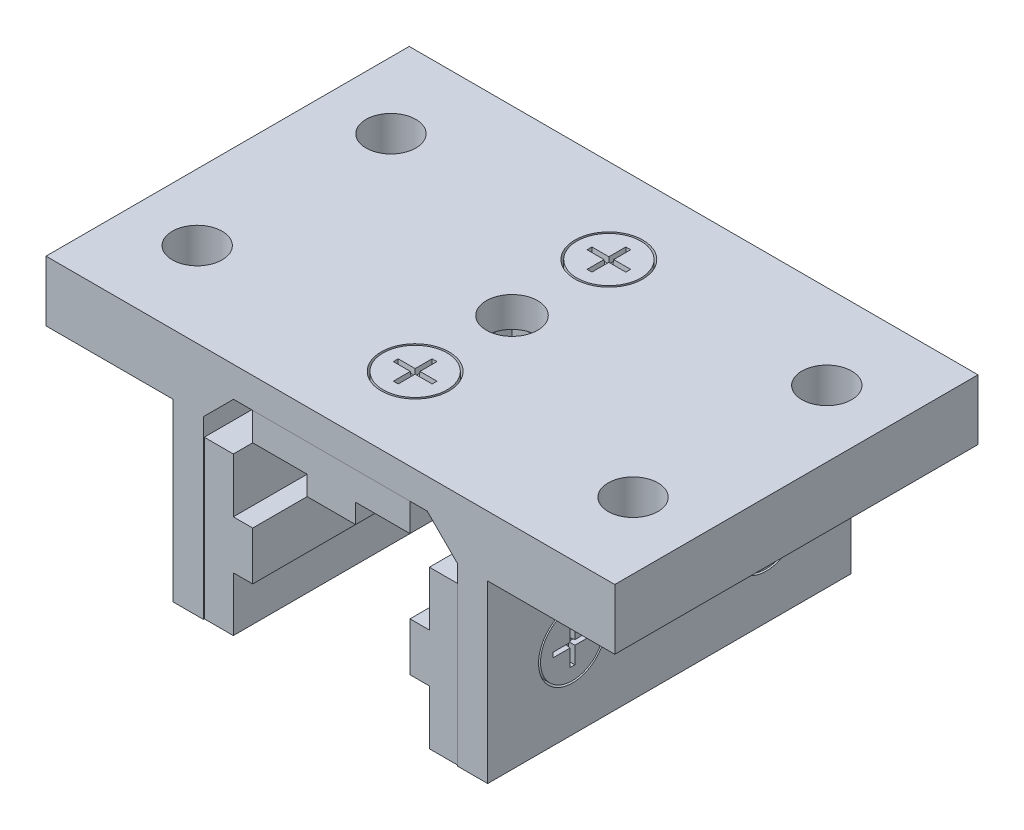
SolidWorks part; units mm, degrees
ref_plane "Front" through (0, 0, 0) normal (0, 0, 1) x (1, 0, 0)
ref_plane "Top" through (0, 0, 0) normal (0, 1, 0) x (1, 0, 0)
ref_plane "Right" through (0, 0, 0) normal (1, 0, 0) x (0, 0, -1)
sketch "Sketch1" plane through (0, 0, 0) normal (0, 0, 1) x (1, 0, 0)
  line L0 (-16.6624, 0) -> (-16.6624, 23.0124)
  line L1 (-20.6248, 30.9372) -> (20.6248, 30.9372)
  line L2 (-20.6248, 30.9372) -> (-20.6248, 0)
  line L3 (-20.6248, 0) -> (-16.6624, 0)
  line L4 (20.6248, 30.9372) -> (20.6248, 0)
  line L5 (-16.6624, 23.0124) -> (-12.7, 26.9748)
  line L6 (-12.7, 26.9748) -> (12.7, 26.9748)
  line L7 (12.7, 26.9748) -> (16.6624, 23.0124)
  line L8 (16.6624, 23.0124) -> (16.6624, 0)
  line L9 (16.6624, 0) -> (20.6248, 0)
  line L11 (-16.6624, 0) -> (16.6624, 0) construction
  dimension "D2" = 45
extrude "Boss-Extrude1" add sketch "Sketch1" along normal mid plane 47.625
sketch "Sketch2" plane through (0, 0, 0) normal (0, 0, 1) x (1, 0, 0)
  line L0 (-12.8524, 13.4874) -> (-12.8524, 20.6248)
  line L1 (-16.6624, 0) -> (-12.8524, 0)
  line L2 (-16.6624, 0) -> (-16.6624, 20.6248)
  line L3 (-16.6624, 20.6248) -> (-12.8524, 20.6248)
  line L4 (-12.8524, 0) -> (-12.8524, 7.1374)
  line L5 (-12.8524, 13.4874) -> (-10.3124, 13.4874)
  line L7 (-12.8524, 7.1374) -> (-10.3124, 7.1374)
  line L8 (-10.3124, 13.4874) -> (-10.3124, 7.1374)
  line L12 (-12.7, 26.9748) -> (12.7, 26.9748) construction
  line L13 (-10.3124, 26.9748) -> (10.3124, 26.9748)
  line L14 (-10.3124, 26.9748) -> (-10.3124, 23.1648)
  line L15 (-10.3124, 23.1648) -> (-3.175, 23.1648)
  line L16 (10.3124, 26.9748) -> (10.3124, 23.1648)
  line L17 (3.175, 23.1648) -> (10.3124, 23.1648)
  line L19 (-3.175, 23.1648) -> (-3.175, 20.6248)
  line L20 (-3.175, 20.6248) -> (3.175, 20.6248)
  line L21 (3.175, 23.1648) -> (3.175, 20.6248)
  point P14 (-10.3124, 10.3124)
  point P28 (0, 26.9748)
  dimension "Pad Wd" = 20.6248
  dimension "Pad Thick 1" = 6.35
  dimension "Pad Thick 2" = 3.81
  dimension "Pad Nose" = 6.35
extrude "Boss-Extrude2" add sketch "Sketch2" along normal mid plane 47.371 separate body
sketch "Sketch11" plane through (-10.3124, 0, 0) normal (1, 0, 0) x (0, 0, -1)
  line L0 (-23.6855, 13.4874) -> (23.6855, 13.4874) construction
  line L1 (-3.175, 13.4874) -> (3.175, 13.4874)
  line L2 (-3.175, 13.4874) -> (-3.175, 7.1374)
  line L3 (-3.175, 7.1374) -> (3.175, 7.1374)
  line L4 (3.175, 13.4874) -> (3.175, 7.1374)
  line L5 (-23.6855, 7.1374) -> (23.6855, 7.1374) construction
  point P8 (0, 13.4874)
extrude "Cut-Extrude5" cut sketch "Sketch11" against normal through all
sketch "Sketch12" plane through (0, 20.6248, 0) normal (0, -1, 0) x (1, 0, 0)
  line L0 (-3.175, 23.6855) -> (-3.175, -23.6855) construction
  line L1 (-3.175, 3.175) -> (3.175, 3.175)
  line L2 (-3.175, 3.175) -> (-3.175, -3.175)
  line L3 (-3.175, -3.175) -> (3.175, -3.175)
  line L4 (3.175, 3.175) -> (3.175, -3.175)
  line L5 (3.175, 23.6855) -> (3.175, -23.6855) construction
  point P8 (-3.175, 0)
extrude "Cut-Extrude6" cut sketch "Sketch12" against normal through all
mirror "Mirror1" about plane through (0, 0, 0) normal (1, 0, 0) of bodies 126 109
sketch "Sketch3" plane through (0, 30.9372, 0) normal (0, 1, 0) x (1, 0, 0)
  line L0 (0, -12.7) -> (0, 12.7) construction
  circle A0 centre (0, -12.7) radius 4.445
  circle A1 centre (0, -12.7) radius 4.191
extrude "Cut-Extrude1" cut sketch "Sketch3" against normal blind 1.9812
sketch "Sketch5" plane through (0, 30.9372, 0) normal (0, 1, 0) x (1, 0, 0)
  line L0 (0.3175, -12.3825) -> (2.54, -12.3825)
  line L1 (-0.3175, -10.16) -> (0.3175, -10.16)
  line L2 (-0.3175, -10.16) -> (-0.3175, -12.3825)
  line L3 (-0.3175, -15.24) -> (0.3175, -15.24)
  line L4 (0.3175, -10.16) -> (0.3175, -12.3825)
  line L5 (-2.54, -12.3825) -> (-0.3175, -12.3825)
  line L6 (-2.54, -12.3825) -> (-2.54, -13.0175)
  line L7 (-2.54, -13.0175) -> (-0.3175, -13.0175)
  line L8 (2.54, -12.3825) -> (2.54, -13.0175)
  line L9 (-0.3175, -13.0175) -> (-0.3175, -15.24)
  line L10 (0.3175, -13.0175) -> (0.3175, -15.24)
  line L11 (0.3175, -13.0175) -> (2.54, -13.0175)
  line L12 (-0.3175, -12.3825) -> (0.3175, -13.0175) construction
  dimension "D1" = 0.635
  dimension "D2" = 5.08
extrude "Cut-Extrude2" cut sketch "Sketch5" against normal blind 0.762 draft 5
sketch "Sketch13" plane through (20.6248, 0, 0) normal (1, 0, 0) x (0, 0, -1)
  circle A0 centre (-12.7, 10.3124) radius 4.445
  dimension "D1" = 8.89
extrude "Cut-Extrude-Thin1" cut sketch "Sketch13" against normal blind 1.9812 thin thin type one direction reverse wall 0.254
sketch "Sketch14" plane through (20.6248, 0, 0) normal (1, 0, 0) x (0, 0, -1)
  line L0 (-13.0175, 9.9949) -> (-13.0175, 7.7724)
  line L1 (-13.0175, 12.8524) -> (-12.3825, 12.8524)
  line L2 (-13.0175, 12.8524) -> (-13.0175, 10.6299)
  line L3 (-13.0175, 7.7724) -> (-12.3825, 7.7724)
  line L4 (-12.3825, 12.8524) -> (-12.3825, 10.6299)
  line L5 (-15.24, 10.6299) -> (-13.0175, 10.6299)
  line L6 (-15.24, 10.6299) -> (-15.24, 9.9949)
  line L7 (-15.24, 9.9949) -> (-13.0175, 9.9949)
  line L8 (-10.16, 10.6299) -> (-10.16, 9.9949)
  line L9 (-12.3825, 10.6299) -> (-10.16, 10.6299)
  line L10 (-12.3825, 9.9949) -> (-12.3825, 7.7724)
  line L11 (-12.3825, 9.9949) -> (-10.16, 9.9949)
  line L12 (-13.0175, 10.6299) -> (-12.3825, 9.9949) construction
  dimension "D1" = 0.635
  dimension "D2" = 5.08
extrude "Cut-Extrude7" cut sketch "Sketch14" against normal blind 0.762 draft 5
mirror "Mirror4" about plane through (0, 0, 0) normal (1, 0, 0) of "Cut-Extrude7", "Cut-Extrude-Thin1"
mirror "Mirror3" about plane through (0, 0, 0) normal (0, 0, 1) of "Mirror4", "Cut-Extrude-Thin1", "Cut-Extrude7", "Cut-Extrude1", "Cut-Extrude2"
sketch "Sketch9" plane through (0, 30.9372, 0) normal (0, 1, 0) x (1, 0, 0)
  circle A0 centre (0, 0) radius 3.3655
  dimension "Top Hole Dia" = 6.731
extrude "Cut-Extrude4" cut sketch "Sketch9" against normal through all
sketch "Sketch15" plane through (0, 0, 0) normal (1, 0, 0) x (0, 0, -1)
  circle A0 centre (0, 10.3124) radius 3.3655
  dimension "Side Wall Hole Dia" = 6.731
extrude "Cut-Extrude8" cut sketch "Sketch15" against normal through all and the other way through all
sketch "Sketch16" plane through (0, 0, 0) normal (0, 0, 1) x (1, 0, 0)
  line L1 (-37.2872, 30.9372) -> (-18.6436, 30.9372)
  line L2 (-37.2872, 30.9372) -> (-37.2872, 23.0124)
  line L3 (-37.2872, 23.0124) -> (-18.6436, 23.0124)
  line L4 (-18.6436, 30.9372) -> (-18.6436, 23.0124)
  line L5 (20.6248, 30.9372) -> (-20.6248, 30.9372) construction
  line L6 (18.6436, 30.9372) -> (37.2872, 30.9372)
  line L7 (18.6436, 30.9372) -> (18.6436, 23.0124)
  line L8 (18.6436, 23.0124) -> (37.2872, 23.0124)
  line L9 (37.2872, 30.9372) -> (37.2872, 23.0124)
  line L10 (-20.6248, 0) -> (-16.6624, 0) construction
  line L11 (16.6624, 0) -> (20.6248, 0) construction
  point P4 (-18.6436, 0)
  point P13 (18.6436, 0)
  dimension "Oall Wd" = 74.5744
  dimension "Top Flange Thickness" = 7.9248
extrude "Top Flange" add sketch "Sketch16" along normal up to surface (23.8125 mm away) and the other way up to surface (23.8125 mm away) up to face at (0, 16.1849, 23.8125) other way up to face at (0, 16.1849, -23.8125)
sketch "Sketch17" plane through (0, 30.9372, 0) normal (0, 1, 0) x (1, 0, 0)
  line L0 (-28.575, 12.7) -> (28.575, -12.7) construction
  line L1 (-28.575, 12.7) -> (28.575, 12.7) construction
  line L2 (-28.575, 12.7) -> (-28.575, -12.7) construction
  line L3 (-28.575, -12.7) -> (28.575, -12.7) construction
  line L4 (28.575, 12.7) -> (28.575, -12.7) construction
  line L5 (-18.6436, 12.7) -> (-20.6248, 12.7) construction
  circle A0 centre (28.575, 12.7) radius 3.2639
  circle A1 centre (28.575, -12.7) radius 3.2639
  circle A2 centre (-28.575, 12.7) radius 3.2639
  circle A3 centre (-28.575, -12.7) radius 3.2639
  dimension "Top Flange Hole Dia" = 6.5278
  dimension "Top Flange Hole Spacing" = 57.15
extrude "Top Flange Hole" cut sketch "Sketch17" against normal through all
ref_axis "Center Axis 1" through (-28.575, 23.0124, 12.7) along (0, 1, 0)
ref_axis "Center Axis 2" through (28.575, 23.0124, -12.7) along (0, 1, 0)
ref_axis "Center Axis 3" through (0, 26.9748, 0) along (0, 1, 0)
ref_axis "Axis1" through (-10.3124, 10.3124, 3.175) along (0.7091, 0, 0.7051)
equation "\"D1@Cut-Extrude1\" = \"Top Thick@Sketch1\" * .5"
equation "\"D1@Sketch13\" = \"Screw Head Dia@Sketch3\""
equation "\"D1@Cut-Extrude-Thin1\" = \"Leg Thick@Sketch1\" * .5"
equation "\"D5@Cut-Extrude-Thin1\" = \"D1@Sketch3\""
equation "\"D1@Cut-Extrude7\" = \"D1@Cut-Extrude2\""
equation "\"D1@Sketch14\" = \"D1@Sketch5\""
equation "\"D2@Sketch14\" = \"D2@Sketch5\""
equation "\"D3@Cut-Extrude7\" = \"D3@Cut-Extrude2\""
